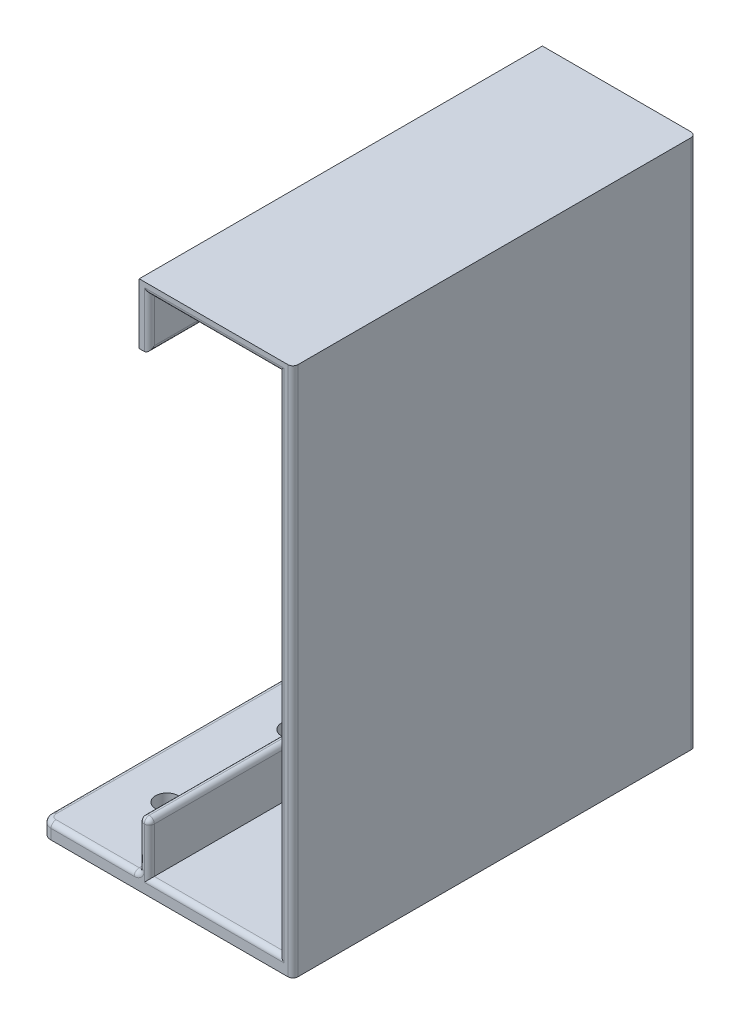
SolidWorks part; units mm, degrees
ref_plane "Front Plane" through (0, 0, 0) normal (0, 0, 1) x (1, 0, 0)
ref_plane "Top Plane" through (0, 0, 0) normal (0, 1, 0) x (1, 0, 0)
ref_plane "Right Plane" through (0, 0, 0) normal (1, 0, 0) x (0, 0, -1)
sketch "Sketch1" plane through (0, 0, 0) normal (0, 1, 0) x (1, 0, 0)
  line L1 (-25, 40) -> (25, 40)
  line L2 (-25, 40) -> (-25, -40)
  line L3 (-25, -40) -> (25, -40)
  line L4 (25, 40) -> (25, -40)
  line L5 (-25, 40) -> (25, -40) construction
  line L6 (-25, -40) -> (25, 40) construction
  point P0 (0, 0)
  dimension "D1" = 50
  dimension "D2" = 80
extrude "Boss-Extrude1" add sketch "Sketch1" along normal blind 3
sketch "Sketch2" plane through (0, 3, 0) normal (0, 1, 0) x (1, 0, 0)
  line L0 (-15, 40) -> (-15, -40) construction
  line L1 (25, 40) -> (-25, 40) construction
  line L2 (-25, -40) -> (25, -40) construction
  circle A0 centre (-15, 0) radius 2.25
  circle A1 centre (-15, 25) radius 2.25
  circle A2 centre (-15, -25) radius 2.25
  dimension "D2" = 4.5
  dimension "D1" = 15
  dimension "D3" = 25
  dimension "D4" = 25
extrude "Cut-Extrude1" cut sketch "Sketch2" against normal through all
sketch "Sketch3" plane through (0, 3, 0) normal (0, 1, 0) x (1, 0, 0)
  line L0 (9.35, -40) -> (9.35, 40) construction
  line L1 (-25, -40) -> (25, -40) construction
  line L2 (25, 40) -> (-25, 40) construction
  line L3 (25, -40) -> (25, 40) construction
  line L4 (-3.3, -55) -> (22, -55) construction
  line L5 (-3.3, -55) -> (-3.3, 45) construction
  line L6 (-3.3, 45) -> (22, 45) construction
  line L7 (22, -55) -> (22, 45) construction
  line L8 (-3.3, -55) -> (22, 45) construction
  line L9 (-3.3, 45) -> (22, -55) construction
  line L10 (22.2, -40) -> (22.2, 40)
  line L11 (25, 40) -> (22.2, 40)
  line L12 (25, -40) -> (25, 40)
  line L13 (-3.5, -40) -> (-3.5, 40)
  line L14 (22.2, -40) -> (25, -40)
  line L15 (22.2, -55) -> (22.2, 45) construction
  line L16 (-5.5, -40) -> (-5.5, 40)
  line L17 (-5.5, -40) -> (-3.5, -40)
  line L18 (-5.5, 40) -> (-3.5, 40)
  line L20 (-5.5, -55) -> (-5.5, 45) construction
  line L21 (-3.5, -55) -> (-3.5, 45) construction
  point P6 (9.35, -5)
  point P13 (9.35, 0)
  dimension "D1" = 25.3
  dimension "D2" = 100
  dimension "D3" = 3
  dimension "D4" = 5
  dimension "D5" = 0.2
  dimension "D6" = 0.2
  dimension "D7" = 2
extrude "Boss-Extrude2" add sketch "Sketch3" along normal blind 10
sketch "Sketch4" plane through (0, 13, 0) normal (0, 1, 0) x (1, 0, 0)
  line L4 (22.2, -40) -> (25, -40)
  line L5 (25, -40) -> (25, 40)
  line L6 (25, 40) -> (22.2, 40)
  line L7 (22.2, 40) -> (22.2, -40)
  line L8 (22.2, -40) -> (25, -40)
  line L9 (25, -40) -> (25, 40)
  line L10 (25, 40) -> (22.2, 40)
  line L11 (22.2, 40) -> (22.2, -40)
  dimension "D1" = 0
extrude "Boss-Extrude3" add sketch "Sketch4" along normal blind 90.2
sketch "Sketch5" plane through (0, 103.2, 0) normal (0, 1, 0) x (1, 0, 0)
  line L1 (25, 40) -> (-5.5, 40)
  line L2 (25, 40) -> (25, -40)
  line L3 (25, -40) -> (-5.5, -40)
  line L4 (-5.5, 40) -> (-5.5, -40)
extrude "Boss-Extrude4" add sketch "Sketch5" along normal blind 2
sketch "Sketch6" plane through (0, 103.2, 0) normal (0, -1, 0) x (1, 0, 0)
  line L0 (22.2, -40) -> (-5.5, -40) construction
  line L1 (-5.5, 40) -> (-3.5, 40)
  line L2 (-5.5, 40) -> (-5.5, -40)
  line L3 (-5.5, -40) -> (-3.5, -40)
  line L4 (-3.5, 40) -> (-3.5, -40)
  dimension "D1" = 2
extrude "Boss-Extrude5" add sketch "Sketch6" along normal blind 10
fillet "Fillet1" radius 1 21 edges at (-5.5, 8, -40) (25, 52.6, 40) (-3.5, 98.2, 40) (9.35, 103.2, 40) (25, 52.6, -40) (-3.5, 93.2, 0) (-3.5, 98.2, -40) (9.35, 103.2, -40) (22.2, 53.1, -40) (9.35, 3, -40) (-3.5, 8, -40) (22.2, 53.1, 40) (-5.5, 8, 40) (-3.5, 13, 0) (-3.5, 8, 40) (9.35, 3, 40) (-5.5, 13, 0) (-5.5, 3, 0) (-15.25, 3, 40) (-15.25, 3, -40) (-25, 3, 0)
fillet "Fillet2" radius 2 4 edges at (-24.7071, 2.7071, 39.7071) (-24.7071, 2.7071, -39.7071) (-25, 1, -40) (-25, 1, 40)
